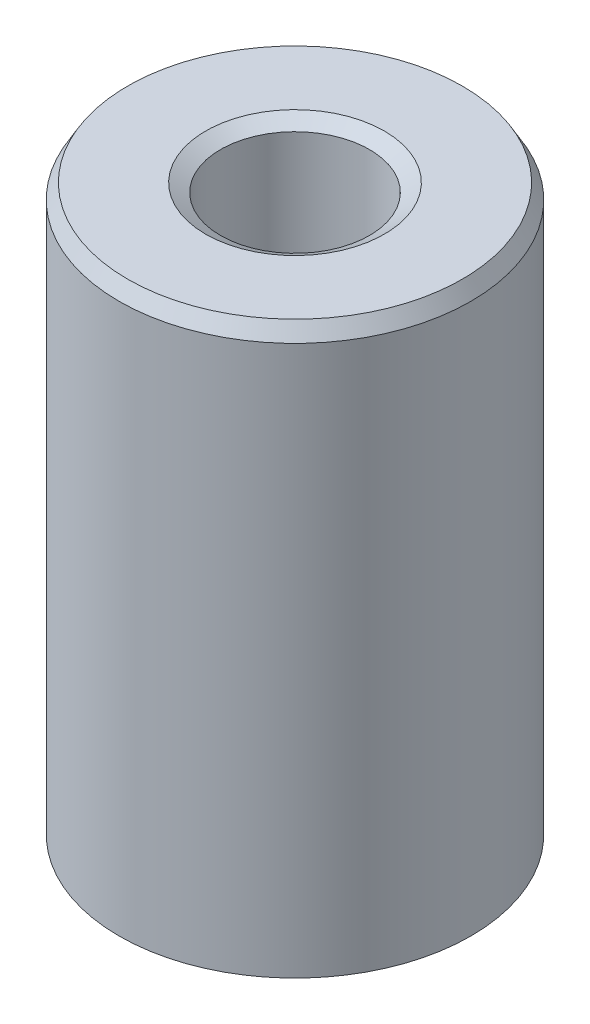
SolidWorks part; units mm, degrees
ref_plane "Front Plane" through (0, 0, 0) normal (0, 0, 1) x (1, 0, 0)
ref_plane "Top Plane" through (0, 0, 0) normal (0, 1, 0) x (1, 0, 0)
ref_plane "Right Plane" through (0, 0, 0) normal (1, 0, 0) x (0, 0, -1)
sketch "Sketch1" plane through (0, 0, 0) normal (0, 1, 0) x (1, 0, 0)
  circle A0 centre (0, 0) radius 17.5
  dimension "SLEEVE_OD" = 35
extrude "Boss-Extrude1" add sketch "Sketch1" along normal blind 57.0157
sketch "Sketch2" plane through (0, 0, 0) normal (0, 1, 0) x (1, 0, 0)
  circle A0 centre (0, 0) radius 7.4114
  dimension "BORE_D" = 14.8229
extrude "Cut-Extrude1" cut sketch "Sketch2" along normal through all
chamfer "Chamfer1" distance 1.4798 angle 30 4 edges at (0, 57.0157, 7.4114) (0, 0, 7.4114) (0, 0, 17.5) (0, 57.0157, 17.5) first distance on face at (0, 57.0157, 7.4114) first distance on face at (0, 0, 7.4114) first distance on face at (0, 57.0157, 17.5)
